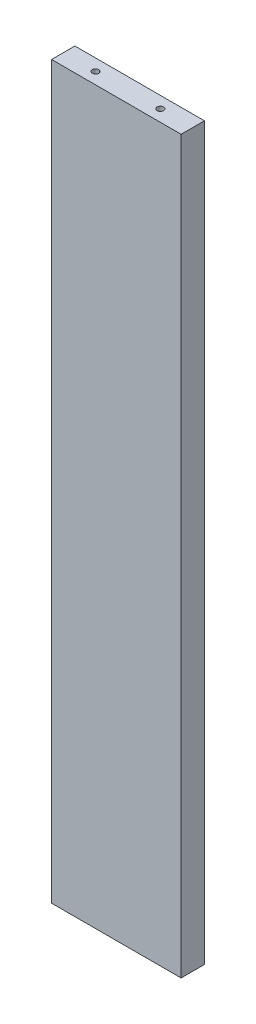
SolidWorks part; units mm, degrees
material "ДСП"
ref_plane "Спереди" through (0, 0, 0) normal (0, 0, 1) x (1, 0, 0)
ref_plane "Сверху" through (0, 0, 0) normal (0, 1, 0) x (1, 0, 0)
ref_plane "Справа" through (0, 0, 0) normal (1, 0, 0) x (0, 0, -1)
sketch "Эскиз1" plane through (0, 0, 0) normal (0, 0, 1) x (1, 0, 0)
  line L1 (0, 0) -> (100, 0)
  line L2 (0, 0) -> (0, 564)
  line L3 (0, 564) -> (100, 564)
  line L4 (100, 0) -> (100, 564)
  dimension "D1" = 564
  dimension "D2" = 100
extrude "Придание толщины" add sketch "Эскиз1" along normal blind 18
sketch "Эскиз3" plane through (0, 0, 18) normal (0, 0, 1) x (1, 0, 0)
  line L0 (0, 564) -> (0, 0) construction
  line L1 (0, 0) -> (100, 0) construction
  circle A0 centre (0, 0) radius 4
  dimension "D1" = 8
  dimension "D2" = 0
  dimension "D3" = 0
extrude "Отверстие 1" [suppressed] cut sketch "Эскиз3" against normal blind 16
sketch "Эскиз4" plane through (0, 0, 18) normal (0, 0, 1) x (1, 0, 0)
  line L0 (0, 564) -> (0, 0) construction
  line L1 (0, 0) -> (100, 0) construction
  circle A0 centre (0, 0) radius 4
  dimension "D2" = 0
  dimension "D3" = 8
extrude "Отверстие 2" [suppressed] cut sketch "Эскиз4" against normal blind 16
sketch "Эскиз5" plane through (0, 0, 18) normal (0, 0, 1) x (1, 0, 0)
  line L0 (0, 564) -> (0, 0) construction
  line L1 (0, 0) -> (100, 0) construction
  circle A0 centre (0, 0) radius 4
  dimension "D1" = 8
extrude "Отверстие 3" [suppressed] cut sketch "Эскиз5" against normal blind 16
sketch "Эскиз6" plane through (0, 0, 18) normal (0, 0, 1) x (1, 0, 0)
  line L0 (0, 564) -> (0, 0) construction
  line L1 (0, 0) -> (100, 0) construction
  circle A0 centre (0, 0) radius 4
  dimension "D1" = 8
extrude "Отверстие 4" [suppressed] cut sketch "Эскиз6" against normal blind 16
sketch "Эскиз7" plane through (0, 0, 18) normal (0, 0, 1) x (1, 0, 0)
  line L0 (0, 564) -> (0, 0) construction
  line L1 (0, 0) -> (100, 0) construction
  circle A0 centre (0, 0) radius 4
  dimension "D1" = 8
extrude "Отверстие 5" [suppressed] cut sketch "Эскиз7" against normal blind 16
sketch "Эскиз8" plane through (0, 0, 18) normal (0, 0, 1) x (1, 0, 0)
  line L0 (0, 564) -> (0, 0) construction
  line L1 (0, 0) -> (100, 0) construction
  circle A0 centre (0, 0) radius 4
  dimension "D1" = 8
extrude "Отверстие 6" [suppressed] cut sketch "Эскиз8" against normal blind 16
sketch "Эскиз9" plane through (0, 0, 18) normal (0, 0, 1) x (1, 0, 0)
  line L0 (0, 564) -> (0, 0) construction
  line L1 (0, 0) -> (100, 0) construction
  circle A0 centre (0, 0) radius 4
  dimension "D1" = 8
extrude "Отверстие 7" [suppressed] cut sketch "Эскиз9" against normal blind 16
sketch "Эскиз10" plane through (0, 0, 18) normal (0, 0, 1) x (1, 0, 0)
  line L0 (0, 564) -> (0, 0) construction
  line L1 (0, 0) -> (100, 0) construction
  circle A0 centre (0, 0) radius 4
  dimension "D1" = 8
extrude "Отверстие 8" [suppressed] cut sketch "Эскиз10" against normal blind 16
sketch "Эскиз27" plane through (0, 0, 18) normal (0, 0, 1) x (1, 0, 0)
  line L2 (0, 564) -> (0, 0) construction
  line L3 (0, 0) -> (100, 0) construction
  circle A0 centre (0, 0) radius 4
  dimension "D1" = 8
  dimension "D3" = 0
extrude "Отверстие 9" [suppressed] cut sketch "Эскиз27" against normal blind 10
sketch "Эскиз29" plane through (0, 0, 18) normal (0, 0, 1) x (1, 0, 0)
  line L2 (0, 564) -> (0, 0) construction
  line L3 (0, 0) -> (100, 0) construction
  circle A0 centre (0, 0) radius 4
  dimension "D1" = 8
extrude "Отверстие 10" [suppressed] cut sketch "Эскиз29" against normal blind 10
sketch "Эскиз30" plane through (0, 0, 18) normal (0, 0, 1) x (1, 0, 0)
  line L1 (0, 0) -> (100, 0) construction
  line L3 (0, 564) -> (0, 0) construction
  circle A0 centre (0, 0) radius 4
  dimension "D1" = 8
extrude "Отверстие 11" [suppressed] cut sketch "Эскиз30" against normal blind 10
sketch "Эскиз31" plane through (0, 0, 18) normal (0, 0, 1) x (1, 0, 0)
  line L2 (0, 0) -> (100, 0) construction
  line L3 (0, 564) -> (0, 0) construction
  circle A0 centre (0, 0) radius 4
  dimension "D1" = 8
extrude "Отверстие 12" [suppressed] cut sketch "Эскиз31" against normal blind 10
sketch "Эскиз11" plane through (0, 564, 0) normal (0, 1, 0) x (1, 0, 0)
  line L0 (0, -18) -> (0, 0) construction
  line L1 (100, -18) -> (0, -18) construction
  circle A0 centre (25, -9) radius 2.5
  dimension "D1" = 5
  dimension "D2" = 25
  dimension "D3" = 9
extrude "Отверстие А1" cut sketch "Эскиз11" against normal blind 37
sketch "Эскиз12" plane through (0, 564, 0) normal (0, 1, 0) x (1, 0, 0)
  line L1 (0, -18) -> (0, 0) construction
  line L2 (100, -18) -> (0, -18) construction
  circle A0 centre (75, -9) radius 2.5
  dimension "D1" = 5
  dimension "D3" = 9
  dimension "D2" = 75
extrude "Отверстие А2" cut sketch "Эскиз12" against normal blind 37
sketch "Эскиз13" plane through (0, 564, 0) normal (0, 1, 0) x (1, 0, 0)
  line L1 (0, -18) -> (0, 0) construction
  line L2 (100, -18) -> (0, -18) construction
  circle A0 centre (0, -18) radius 4
  dimension "D1" = 8
  dimension "D3" = 0
extrude "Отверстие А3" [suppressed] cut sketch "Эскиз13" against normal blind 20
sketch "Эскиз14" plane through (0, 564, 0) normal (0, 1, 0) x (1, 0, 0)
  line L0 (0, -18) -> (0, 0) construction
  line L1 (100, -18) -> (0, -18) construction
  circle A0 centre (0, -10) radius 4
  dimension "D1" = 8
  dimension "D3" = 8
extrude "Отверстие А4" [suppressed] cut sketch "Эскиз14" against normal blind 20
sketch "Эскиз15" plane through (100, 0, 0) normal (1, 0, 0) x (0, 0, -1)
  line L0 (-18, 564) -> (0, 564) construction
  line L1 (-18, 0) -> (-18, 564) construction
  circle A0 centre (-18, 564) radius 2.5
  dimension "D2" = 0
  dimension "D3" = 0
  dimension "D1" = 5
extrude "Отверстие В1" [suppressed] cut sketch "Эскиз15" against normal blind 37
sketch "Эскиз16" plane through (100, 0, 0) normal (1, 0, 0) x (0, 0, -1)
  line L0 (-18, 564) -> (0, 564) construction
  line L1 (-18, 0) -> (-18, 564) construction
  circle A0 centre (-18, 564) radius 2.5
  dimension "D1" = 5
extrude "Отверстие В2" [suppressed] cut sketch "Эскиз16" against normal blind 37
sketch "Эскиз17" plane through (100, 0, 0) normal (1, 0, 0) x (0, 0, -1)
  line L1 (-18, 564) -> (0, 564) construction
  line L2 (-18, 0) -> (-18, 564) construction
  circle A0 centre (-18, 564) radius 4
  dimension "D1" = 8
  dimension "D2" = 0
  dimension "D3" = 0
extrude "Отверстие В3" [suppressed] cut sketch "Эскиз17" against normal blind 20
sketch "Эскиз18" plane through (100, 0, 0) normal (1, 0, 0) x (0, 0, -1)
  line L0 (-18, 564) -> (0, 564) construction
  line L1 (-18, 0) -> (-18, 564) construction
  circle A0 centre (-18, 564) radius 4
  dimension "D3" = 0
  dimension "D1" = 0
  dimension "D2" = 8
extrude "Отверстие В4" [suppressed] cut sketch "Эскиз18" against normal blind 20
sketch "Эскиз19" plane through (0, 0, 0) normal (0, -1, 0) x (1, 0, 0)
  line L0 (100, 18) -> (100, 0) construction
  line L1 (0, 18) -> (100, 18) construction
  circle A0 centre (75, 9) radius 2.5
  dimension "D1" = 5
  dimension "D2" = 25
  dimension "D3" = 9
extrude "Отверстие С1" cut sketch "Эскиз19" against normal blind 37
sketch "Эскиз20" plane through (0, 0, 0) normal (0, -1, 0) x (1, 0, 0)
  line L0 (100, 18) -> (100, 0) construction
  line L1 (0, 18) -> (100, 18) construction
  circle A0 centre (25, 9) radius 2.5
  dimension "D3" = 9
  dimension "D2" = 5
  dimension "D1" = 75
extrude "Отверстие С2" cut sketch "Эскиз20" against normal blind 37
sketch "Эскиз21" plane through (0, 0, 0) normal (0, -1, 0) x (1, 0, 0)
  line L0 (100, 18) -> (100, 0) construction
  line L1 (0, 18) -> (100, 18) construction
  circle A0 centre (100, 18) radius 4
  dimension "D1" = 8
  dimension "D2" = 0
  dimension "D3" = 0
extrude "Отверстие С3" [suppressed] cut sketch "Эскиз21" against normal blind 20
sketch "Эскиз22" plane through (0, 0, 0) normal (0, -1, 0) x (1, 0, 0)
  line L0 (100, 18) -> (100, 0) construction
  line L1 (0, 18) -> (100, 18) construction
  circle A0 centre (100, 18) radius 4
  dimension "D1" = 8
  dimension "D2" = 0
  dimension "D3" = 0
extrude "Отверстие С4" [suppressed] cut sketch "Эскиз22" against normal blind 20
sketch "Эскиз23" plane through (0, 0, 0) normal (-1, 0, 0) x (0, 0, 1)
  line L0 (18, 0) -> (0, 0) construction
  line L1 (18, 564) -> (18, 0) construction
  circle A0 centre (18, 0) radius 2.5
  dimension "D2" = 0
  dimension "D3" = 0
  dimension "D1" = 5
extrude "Отверстие Д1" [suppressed] cut sketch "Эскиз23" against normal blind 37
sketch "Эскиз24" plane through (0, 0, 0) normal (-1, 0, 0) x (0, 0, 1)
  line L0 (18, 0) -> (0, 0) construction
  line L1 (18, 564) -> (18, 0) construction
  circle A0 centre (18, 0) radius 2.5
  dimension "D2" = 0
  dimension "D3" = 0
  dimension "D1" = 5
extrude "Отверстие Д2" [suppressed] cut sketch "Эскиз24" against normal blind 37
sketch "Эскиз25" plane through (0, 0, 0) normal (-1, 0, 0) x (0, 0, 1)
  line L0 (18, 0) -> (0, 0) construction
  line L1 (18, 564) -> (18, 0) construction
  circle A0 centre (18, 0) radius 4
  dimension "D1" = 8
  dimension "D2" = 0
  dimension "D3" = 0
extrude "Отверстие Д3" [suppressed] cut sketch "Эскиз25" against normal blind 20
sketch "Эскиз26" plane through (0, 0, 0) normal (-1, 0, 0) x (0, 0, 1)
  line L0 (18, 0) -> (0, 0) construction
  line L1 (18, 564) -> (18, 0) construction
  circle A0 centre (18, 0) radius 4
  dimension "D1" = 8
  dimension "D2" = 0
  dimension "D3" = 0
extrude "Отверстие Д4" [suppressed] cut sketch "Эскиз26" against normal blind 20
equation "\"D1@Придание толщины\" = \"Thick\""
equation "\"D2@Эскиз1\"=\"Width\""
equation "\"D1@Эскиз1\"=\"Height\""
equation "\"D1\" = 0"
equation "\"X1\" = 0"
equation "\"Y1\" = 0"
equation "\"H1\" = 0"
equation "\"D1@Эскиз3\"=\"D1\""
equation "\"D2@Эскиз3\"=\"X1\""
equation "\"D3@Эскиз3\"=\"Y1\""
equation "\"D1@Отверстие 1\"=\"H1\""
equation "\"D2\" = 0"
equation "\"X2\" = 0"
equation "\"Y2\" = 0"
equation "\"H2\" = 0"
equation "\"D3\" = 0"
equation "\"X3\" = 0"
equation "\"Y3\" = 0"
equation "\"H3\" = 0"
equation "\"D4\" = 0"
equation "\"X4\" = 0"
equation "\"Y4\" = 0"
equation "\"H4\" = 0"
equation "\"D5\" = 0"
equation "\"X5\" = 0"
equation "\"Y5\" = 0"
equation "\"H5\" = 0"
equation "\"D6\" = 0"
equation "\"X6\" = 0"
equation "\"Y6\" = 0"
equation "\"H6\" = 0"
equation "\"D7\" = 0"
equation "\"X7\" = 0"
equation "\"Y7\" = 0"
equation "\"H7\" = 0"
equation "\"D8\" = 0"
equation "\"X8\" = 0"
equation "\"Y8\" = 0"
equation "\"H8\" = 0"
equation "\"D3@Эскиз4\"=\"D2\""
equation "\"D1@Эскиз4\"=\"X2\""
equation "\"D2@Эскиз4\"=\"Y2\""
equation "\"D1@Отверстие 2\"=\"H2\""
equation "\"D2@Эскиз5\"=\"X3\""
equation "\"D1@Эскиз5\"=\"D3\""
equation "\"D3@Эскиз5\"=\"Y3\""
equation "\"D1@Отверстие 3\" = \"H3\""
equation "\"D1@Эскиз6\"=\"D4\""
equation "\"D2@Эскиз6\"=\"X4\""
equation "\"D3@Эскиз6\"=\"Y4\""
equation "\"D1@Отверстие 4\" = \"H4\""
equation "\"D1@Эскиз7\"=\"D5\""
equation "\"D2@Эскиз7\"=\"X5\""
equation "\"D3@Эскиз7\"=\"Y5\""
equation "\"D1@Отверстие 5\" = \"H5\""
equation "\"D1@Эскиз8\"=\"D6\""
equation "\"D2@Эскиз8\"=\"X6\""
equation "\"D3@Эскиз8\"=\"Y6\""
equation "\"D1@Отверстие 6\" = \"H6\""
equation "\"D1@Эскиз9\"=\"D7\""
equation "\"D2@Эскиз9\"=\"X7\""
equation "\"D3@Эскиз9\"=\"Y7\""
equation "\"D1@Отверстие 7\" = \"H7\""
equation "\"D1@Эскиз10\"=\"D8\""
equation "\"D2@Эскиз10\"=\"X8\""
equation "\"D3@Эскиз10\"=\"Y8\""
equation "\"D1@Отверстие 8\" = \"H8\""
equation "\"Отверстие 1\"= IIF ( \"D1\" = 0 , \"suppressed\" , \"unsuppressed\" )"
equation "\"Отверстие 2\"= IIF ( \"D2\" = 0 , \"suppressed\" , \"unsuppressed\" )"
equation "\"Отверстие 3\"= IIF ( \"D3\" = 0 , \"suppressed\" , \"unsuppressed\" )"
equation "\"Отверстие 4\"= IIF ( \"D4\" = 0 , \"suppressed\" , \"unsuppressed\" )"
equation "\"Отверстие 5\"= IIF ( \"D5\" = 0 , \"suppressed\" , \"unsuppressed\" )"
equation "\"Отверстие 6\" = IIF ( \"D6\" = 0 , \"suppressed\" , \"unsuppressed\" )"
equation "\"Отверстие 7\"= IIF ( \"D7\" = 0 , \"suppressed\" , \"unsuppressed\" )"
equation "\"Отверстие 8\"= IIF ( \"D8\" = 0 , \"suppressed\" , \"unsuppressed\" )"
equation "\"DA1\" = 5"
equation "\"XA1\" = 25"
equation "\"YA1\" = 9"
equation "\"HA1\" = 37"
equation "\"DA2\" = 5"
equation "\"XA2\" = 75"
equation "\"YA2\" = 9"
equation "\"HA2\" = 37"
equation "\"DA3\" = 0"
equation "\"XA3\" = 0"
equation "\"YA3\" = 0"
equation "\"DA4\" = 0"
equation "\"XA4\" = 0"
equation "\"YA4\" = 0"
equation "\"HA4\" = 0"
equation "\"D1@Эскиз11\"=\"DA1\""
equation "\"D2@Эскиз11\"=\"XA1\""
equation "\"D3@Эскиз11\"=\"YA1\""
equation "\"D1@Отверстие А1\" = \"HA1\""
equation "\"D1@Эскиз12\"=\"DA2\""
equation "\"D2@Эскиз12\"=\"XA2\""
equation "\"HA3\" = 0"
equation "\"D1@Эскиз13\"=\"DA3\""
equation "\"D2@Эскиз13\"=\"XA3\""
equation "\"D3@Эскиз13\"=\"YA3\""
equation "\"D1@Отверстие А3\" = \"HA3\""
equation "\"D1@Отверстие А2\" = \"HA2\""
equation "\"D1@Эскиз14\"=\"DA4\""
equation "\"D2@Эскиз14\"=\"XA4\""
equation "\"Отверстие А1\"= IIF ( \"DA1\" = 0 , \"suppressed\" , \"unsuppressed\" )"
equation "\"Отверстие А2\"= IIF ( \"DA2\" = 0 , \"suppressed\" , \"unsuppressed\" )"
equation "\"Отверстие А3\"= IIF ( \"DA3\" = 0 , \"suppressed\" , \"unsuppressed\" )"
equation "\"Отверстие А4\"= IIF ( \"DA4\" = 0 , \"suppressed\" , \"unsuppressed\" )"
equation "\"DB1\" = 0"
equation "\"XB1\" = 0"
equation "\"YB1\" = 0"
equation "\"HB1\" = 0"
equation "\"DB2\" = 0"
equation "\"XB2\" = 0"
equation "\"YB2\" = 0"
equation "\"HB2\" = 0"
equation "\"DB3\" = 0"
equation "\"XB3\" = 0"
equation "\"YB3\" = 0"
equation "\"HB3\" = 0"
equation "\"DB4\" = 0"
equation "\"XB4\" = 0"
equation "\"YB4\" = 0"
equation "\"HB4\" = 0"
equation "\"DC1\" = 5"
equation "\"XC1\" = 25"
equation "\"YC1\" = 9"
equation "\"HC1\" = 37"
equation "\"DC2\" = 5"
equation "\"XC2\" = 75"
equation "\"YC2\" = 9"
equation "\"HC2\" = 37"
equation "\"DC3\" = 0"
equation "\"XC3\" = 0"
equation "\"YC3\" = 0"
equation "\"HC3\" = 0"
equation "\"DC4\" = 0"
equation "\"XC4\" = 0"
equation "\"YC4\" = 0"
equation "\"HC4\" = 0"
equation "\"DD1\" = 0"
equation "\"XD1\" = 0"
equation "\"YD1\" = 0"
equation "\"HD1\" = 0"
equation "\"DD2\" = 0"
equation "\"XD2\" = 0"
equation "\"YD2\" = 0"
equation "\"HD2\" = 0"
equation "\"DD3\" = 0"
equation "\"XD3\" = 0"
equation "\"YD3\" = 0"
equation "\"HD3\" = 0"
equation "\"DD4\" = 0"
equation "\"XD4\" = 0"
equation "\"YD4\" = 0"
equation "\"HD4\" = 0"
equation "\"D1@Эскиз15\"=\"DB1\""
equation "\"D2@Эскиз15\"=\"XB1\""
equation "\"D3@Эскиз15\"=\"YB1\""
equation "\"D1@Отверстие В1\" = \"HB1\""
equation "\"D1@Эскиз16\"=\"DB2\""
equation "\"D2@Эскиз16\"=\"XB2\""
equation "\"D3@Эскиз16\"=\"YB2\""
equation "\"D1@Отверстие В2\" = \"HB2\""
equation "\"D1@Эскиз17\"=\"DB3\""
equation "\"D2@Эскиз17\"=\"XB3\""
equation "\"D3@Эскиз17\"=\"YB3\""
equation "\"D1@Отверстие В3\" = \"HB3\""
equation "\"D1@Эскиз18\"=\"XB4\""
equation "\"D2@Эскиз18\"=\"DB4\""
equation "\"D3@Эскиз18\"=\"YB4\""
equation "\"D1@Отверстие В4\" = \"HB4\""
equation "\"D1@Эскиз19\"=\"DC1\""
equation "\"D2@Эскиз19\"=\"XC1\""
equation "\"D3@Эскиз19\"=\"YC1\""
equation "\"D1@Отверстие С1\" = \"HC1\""
equation "\"D1@Эскиз20\"=\"XC2\""
equation "\"D2@Эскиз20\"=\"DC2\""
equation "\"D3@Эскиз20\"=\"YC2\""
equation "\"D1@Отверстие С2\" = \"HC2\""
equation "\"D1@Эскиз21\"=\"DC3\""
equation "\"D2@Эскиз21\"=\"XC3\""
equation "\"D3@Эскиз21\"=\"YC3\""
equation "\"D1@Отверстие С3\" = \"HC3\""
equation "\"D1@Эскиз22\"=\"DC4\""
equation "\"D2@Эскиз22\"=\"XC4\""
equation "\"D3@Эскиз22\"=\"YC4\""
equation "\"D1@Отверстие С4\" = \"HC4\""
equation "\"D1@Эскиз23\"=\"DD1\""
equation "\"D2@Эскиз23\"=\"XD1\""
equation "\"D3@Эскиз23\"=\"YD1\""
equation "\"D1@Отверстие Д1\" = \"HD1\""
equation "\"D1@Эскиз24\"=\"DD2\""
equation "\"D2@Эскиз24\"=\"XD2\""
equation "\"D3@Эскиз24\"=\"YD2\""
equation "\"D1@Отверстие Д2\" = \"HD2\""
equation "\"D1@Эскиз25\"=\"DD3\""
equation "\"D2@Эскиз25\"=\"XD3\""
equation "\"D3@Эскиз25\"=\"YD3\""
equation "\"D1@Отверстие Д3\" = \"HD3\""
equation "\"D1@Эскиз26\"=\"DD4\""
equation "\"D2@Эскиз26\"=\"XD4\""
equation "\"D3@Эскиз26\"=\"YD4\""
equation "\"D1@Отверстие Д4\" = \"HD4\""
equation "\"Отверстие В1\"= IIF ( \"DB1\" = 0 , \"suppressed\" , \"unsuppressed\" )"
equation "\"Отверстие В2\"= IIF ( \"DB2\" = 0 , \"suppressed\" , \"unsuppressed\" )"
equation "\"Отверстие В3\"= IIF ( \"DB3\" = 0 , \"suppressed\" , \"unsuppressed\" )"
equation "\"Отверстие В4\"= IIF ( \"DB4\" = 0 , \"suppressed\" , \"unsuppressed\" )"
equation "\"Отверстие С1\"= IIF ( \"DC1\" = 0 , \"suppressed\" , \"unsuppressed\" )"
equation "\"Отверстие С2\"= IIF ( \"DC2\" = 0 , \"suppressed\" , \"unsuppressed\" )"
equation "\"Отверстие С3\"= IIF ( \"DC3\" = 0 , \"suppressed\" , \"unsuppressed\" )"
equation "\"Отверстие С4\"= IIF ( \"DC4\" = 0 , \"suppressed\" , \"unsuppressed\" )"
equation "\"Отверстие Д1\"= IIF ( \"DD1\" = 0 , \"suppressed\" , \"unsuppressed\" )"
equation "\"Отверстие Д2\"= IIF ( \"DD2\" = 0 , \"suppressed\" , \"unsuppressed\" )"
equation "\"Отверстие Д3\"= IIF ( \"DD3\" = 0 , \"suppressed\" , \"unsuppressed\" )"
equation "\"Отверстие Д4\"= IIF ( \"DD4\" = 0 , \"suppressed\" , \"unsuppressed\" )"
equation "\"D9\" = 0"
equation "\"X9\" = 0"
equation "\"Y9\" = 0"
equation "\"H9\" = 0"
equation "\"D10\" = 0"
equation "\"X10\" = 0"
equation "\"Y10\" = 0"
equation "\"H10\" = 0"
equation "\"D11\" = 0"
equation "\"X11\" = 0"
equation "\"Y11\" = 0"
equation "\"H11\" = 0"
equation "\"D12\" = 0"
equation "\"X12\" = 0"
equation "\"Y12\" = 0"
equation "\"H12\" = 0"
equation "\"D1@Эскиз27\"=\"D9\""
equation "\"D2@Эскиз27\"=\"X9\""
equation "\"D3@Эскиз27\"=\"Y9\""
equation "\"D1@Отверстие 9\" = \"H9\""
equation "\"D1@Эскиз29\"=\"D10\""
equation "\"D2@Эскиз29\"=\"X10\""
equation "\"D3@Эскиз29\"=\"Y10\""
equation "\"D1@Отверстие 10\" = \"H10\""
equation "\"D1@Эскиз30\"=\"D11\""
equation "\"D2@Эскиз30\"=\"X11\""
equation "\"D3@Эскиз30\"=\"Y11\""
equation "\"D1@Отверстие 11\" = \"H11\""
equation "\"D1@Эскиз31\"=\"D12\""
equation "\"D2@Эскиз31\"=\"X12\""
equation "\"D3@Эскиз31\"=\"Y12\""
equation "\"D1@Отверстие 12\" = \"H12\""
equation "\"Отверстие 9\"= IIF ( \"D9\" = 0 , \"suppressed\" , \"unsuppressed\" )"
equation "\"Отверстие 10\"= IIF ( \"D10\" = 0 , \"suppressed\" , \"unsuppressed\" )"
equation "\"Отверстие 11\"= IIF ( \"D11\" = 0 , \"suppressed\" , \"unsuppressed\" )"
equation "\"Отверстие 12\"= IIF ( \"D12\" = 0 , \"suppressed\" , \"unsuppressed\" )"
equation "\"Height\" = 564"
equation "\"Width\" = 100"
equation "\"Thick\" = 18"
equation "\"D3@Эскиз12\"=\"YA2\""
